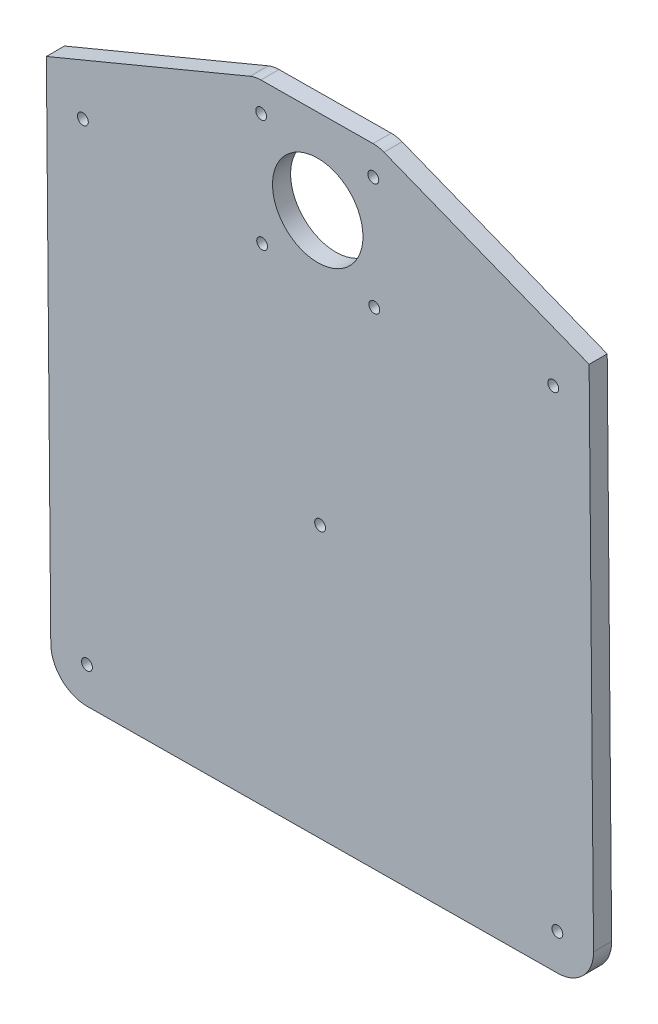
SolidWorks part; units mm, degrees
ref_plane "Front Plane" through (0, 0, 0) normal (0, 0, 1) x (1, 0, 0)
ref_plane "Top Plane" through (0, 0, 0) normal (0, 1, 0) x (1, 0, 0)
ref_plane "Right Plane" through (0, 0, 0) normal (1, 0, 0) x (0, 0, -1)
sketch "Sketch1" plane through (0, 0, 0) normal (0, 1, 0) x (1, 0, 0)
  line L1 (-75, -75) -> (65, -75)
  line L3 (-75, 75) -> (65, 75)
  line L4 (75, -65) -> (75, 65)
  line L5 (-75, -75) -> (75, 75) construction
  line L6 (-75, 75) -> (75, -75) construction
  line L11 (-90.5, -15.5) -> (-59.5, 15.5) construction
  line L12 (-90.5, 15.5) -> (-59.5, -15.5) construction
  line L16 (-97.9134, -18.5069) -> (-75, -75)
  line L17 (-98.5, -15.5) -> (-98.5, 15.5)
  line L18 (-98.5, 0) -> (-75, 0) construction
  line L19 (-97.9134, 18.5069) -> (-75, 75)
  circle A0 centre (-90.5, 15.5) radius 1.5
  circle A1 centre (-90.5, -15.5) radius 1.5
  circle A2 centre (-59.5, -15.5) radius 1.5
  circle A3 centre (-59.5, 15.5) radius 1.5
  circle A4 centre (-75, 0) radius 12.5
  arc A5 (-98.5, -15.5) -> (-97.9134, -18.5069) centre (-90.5, -15.5) ccw
  arc A6 (-98.5, 15.5) -> (-97.9134, 18.5069) centre (-90.5, 15.5) cw
  arc A7 (65, -75) -> (75, -65) centre (65, -65) ccw
  arc A8 (65, 75) -> (75, 65) centre (65, 65) cw
  circle A9 centre (-65, 65) radius 1.5
  circle A10 centre (65, 65) radius 1.5
  circle A11 centre (65, -65) radius 1.5
  circle A12 centre (-65, -65) radius 1.5
  circle A13 centre (0, 0) radius 1.5
  point P0 (0, 0)
  point P6 (-75, 0)
  dimension "D3" = 3
  dimension "D2" = 25
  dimension "D6" = 10
  dimension "D7" = 3
  dimension "D8" = 3
  dimension "D1" = 150
  dimension "D4" = 31
  dimension "D5" = 8
extrude "Boss-Extrude1" add sketch "Sketch1" along normal blind 5
move or copy body "Body-Move/Copy1" bodies to move or copy 101 copy no rotation origin (-6.9519, -2.2564, 4.7564) rotation axis (-0.5807, 0.5757, -0.5757) rotation angle 119.712
move or copy body "Body-Move/Copy2" bodies to move or copy 102 copy no translate (11.6475, 9.2496, 0)
